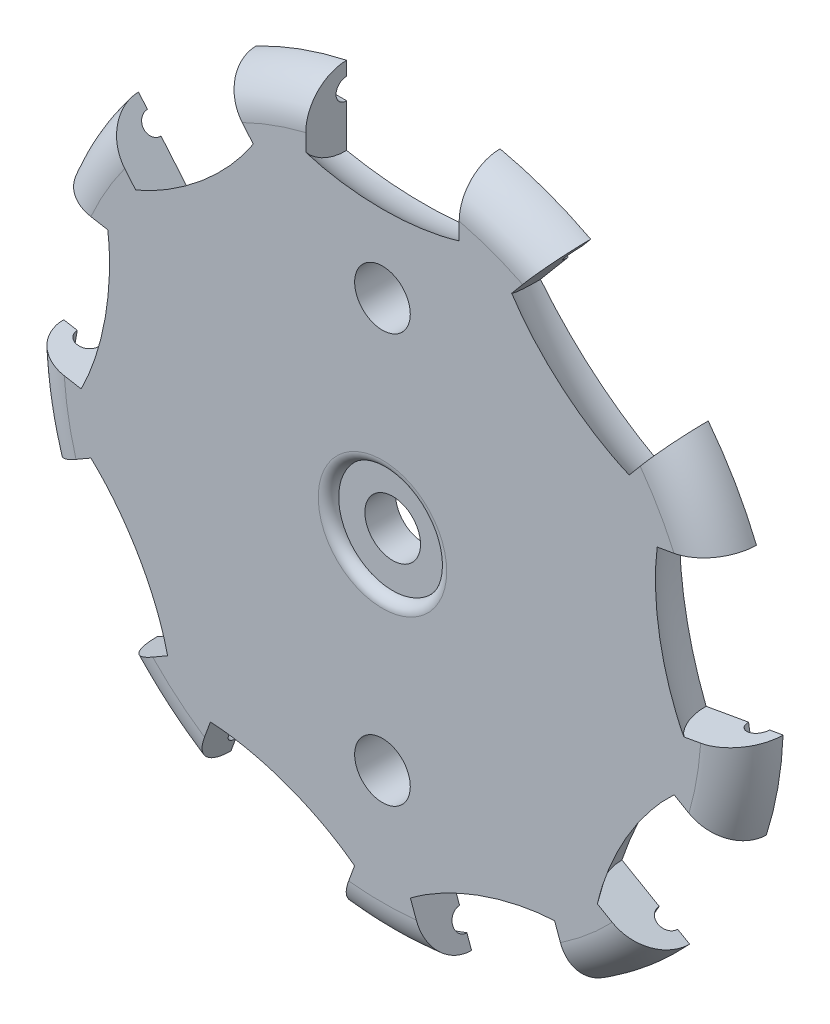
SolidWorks part; units mm, degrees
ref_plane "Front Plane" through (0, 0, 0) normal (0, 0, 1) x (1, 0, 0)
ref_plane "Top Plane" through (0, 0, 0) normal (0, 1, 0) x (1, 0, 0)
ref_plane "Right Plane" through (0, 0, 0) normal (1, 0, 0) x (0, 0, -1)
sketch "Sketch1" plane through (0, 0, 0) normal (0, 0, 1) x (1, 0, 0)
  circle A0 centre (0, 0) radius 27.94
  dimension "D1" = 55.88
extrude "Boss-Extrude1" add sketch "Sketch1" along normal blind 3.175
fillet "Fillet1" radius 3.1852 1 edges at (27.94, 0, 3.175)
sketch "Sketch2" plane through (0, 0, 3.175) normal (0, 0, 1) x (1, 0, 0)
  line L0 (0, -15.875) -> (0, 15.875) construction
  line L1 (0, 0) -> (0, 6.4682) construction
  circle A0 centre (0, 15.875) radius 2.159
  circle A1 centre (0, -15.875) radius 2.159
  circle A4 centre (0, 0) radius 2.159
  point P9 (0, 0)
  dimension "D2" = 4.318
  dimension "D4" = 4.318
  dimension "D1" = 15.875
  dimension "D3" = 2
extrude "Cut-Extrude1" cut sketch "Sketch2" against normal through all
sketch "Sketch5" plane through (0, 0, 0) normal (0, 0, 1) x (1, 0, 0)
  line L0 (-5.9531, 25.4) -> (5.9531, 25.4)
  line L1 (5.9531, 25.4) -> (5.9531, 29.5692)
  line L2 (-5.9531, 25.4) -> (-5.9531, 29.5692)
  line L3 (-5.9531, 25.4) -> (-8.5086, 25.4) construction
  arc A0 (-5.9531, 29.5692) -> (5.9531, 29.5692) centre (0, 0) cw
  circle A1 centre (0, 0) radius 27.94 construction
  point P5 (0, 25.4)
  point P9 (0, 30.1625)
  dimension "D1" = 11.9062
  dimension "D2" = 25.4
  dimension "D3" = 9.525
revolve "Cut-Revolve1" cut sketch "Sketch5" angle 360 about L3
sketch "Sketch6" plane through (0, 0, 0) normal (1, 0, 0) x (0, 0, -1)
  line L0 (0, -27.94) -> (0, 27.2984) construction
  circle A0 centre (0, 25.4) radius 0.8255
  arc A1 (-3.175, 22.6979) -> (0, 21.2308) centre (0, 25.4) ccw construction
  dimension "D1" = 1.651
extrude "Cut-Extrude2" cut sketch "Sketch6" against normal mid plane 15.875
pattern_circular "CirPattern1" count 9 over 360 about axis through (0, 0, 0) along (0, 0, 1) of "Cut-Revolve1", "Cut-Extrude2"
sketch "Sketch8" plane through (0, 0, 3.175) normal (0, 0, 1) x (1, 0, 0)
  line L1 (0, 5.1326) -> (-4.445, 2.5663)
  line L2 (-4.445, 2.5663) -> (-4.445, -2.5663)
  line L3 (-4.445, -2.5663) -> (0, -5.1326)
  line L4 (0, -5.1326) -> (4.445, -2.5663)
  line L5 (4.445, -2.5663) -> (4.445, 2.5663)
  line L6 (4.445, 2.5663) -> (0, 5.1326)
  circle A0 centre (0, 0) radius 4.445 construction
  dimension "D1" = 8.89
extrude "Cut-Extrude4" [suppressed] cut sketch "Sketch8" against normal blind 1.5875
sketch "Sketch9" plane through (0, 0, 3.175) normal (0, 0, 1) x (1, 0, 0)
  circle A0 centre (0, 0) radius 4.191
  dimension "D1" = 8.382
extrude "Cut-Extrude5" cut sketch "Sketch9" against normal blind 0.7937
fillet "Fillet2" radius 0.7937 1 edges at (4.191, 0, 3.175)
